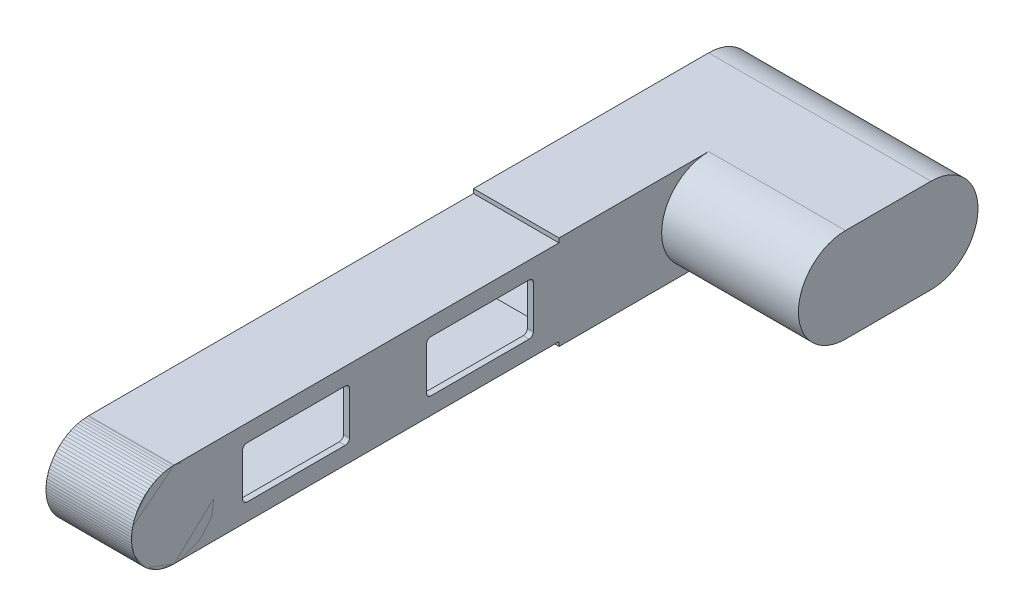
SolidWorks part; units mm, degrees
material "Cast Stainless Steel"
ref_plane "Front Plane" through (0, 0, 0) normal (0, 0, 1) x (1, 0, 0)
ref_plane "Top Plane" through (0, 0, 0) normal (0, 1, 0) x (1, 0, 0)
ref_plane "Right Plane" through (0, 0, 0) normal (1, 0, 0) x (0, 0, -1)
other "Center of Mass"
sketch "Sketch1" plane through (0, 0, 0) normal (1, 0, 0) x (0, 0, -1)
  line L0 (0, 0) -> (-500, 0) construction
  line L5 (-500, 50) -> (-50, 50)
  line L6 (50, -55) -> (-50, -55)
  line L7 (50, -55) -> (50, 55)
  line L8 (50, 55) -> (-50, 55)
  line L9 (-50, -55) -> (-50, 55)
  line L10 (50, -55) -> (-50, 55) construction
  line L11 (50, 55) -> (-50, -55) construction
  line L12 (-500, -50) -> (-50, -50)
  line L13 (0, 0) -> (280, 0)
  line L15 (280, 0) -> (50, 0)
  line L16 (280, 0) -> (280, 55)
  line L17 (280, 55) -> (50, 55)
  line L18 (50, 0) -> (50, 55)
  line L19 (280, 0) -> (50, 0)
  line L20 (280, 0) -> (280, -55)
  line L21 (280, -55) -> (50, -55)
  line L22 (50, 0) -> (50, -55)
  circle A0 centre (-500, 0) radius 50
  dimension "D1" = 100
  dimension "D2" = 110
  dimension "D3" = 100
  dimension "D4" = 500
  dimension "D5" = 280
extrude "Boss-Extrude1" add sketch "Sketch1" along normal blind 100 contours A0 L9 | A0 | L9 L6 L7 L8 | L21 L20 L13 L7 | L16 L17 L7 L13 region at (0, 0, 255.5167) region at (0, 0, 500) region at (0, 52.5, 48.5134) region at (0, 27.5, -165) region at (0, -27.5, -165)
sketch "Sketch2" plane through (0, 55, 0) normal (0, 1, 0) x (1, 0, 0)
  line L0 (0, 280) -> (260, 280)
  line L1 (260, 280) -> (260, 70)
  line L2 (260, 70) -> (100, 70)
  line L4 (0, 280) -> (0, -50)
  line L5 (0, -50) -> (100, -50)
  line L6 (100, -50) -> (100, 280)
  line L7 (100, 280) -> (0, 280)
  line L8 (0, 280) -> (0, -50)
  line L10 (100, -50) -> (100, 280)
  line L11 (100, 280) -> (0, 280)
  line L15 (0, -50) -> (100, -50)
  line M9 (100, -50) -> (100, 280)
  dimension "D2" = 260
  dimension "D3" = 210
  dimension "D1" = 0
extrude "Boss-Extrude2" add sketch "Sketch2" against normal up to surface (110 mm away) contours L2 L1 L0 M9 region at (180, 55, -175) up to face at (50, -55, -115)
sketch "Sketch3" plane through (260, 0, 0) normal (1, 0, 0) x (0, 0, -1)
  line L4 (70, -55) -> (280, -55)
  line L5 (280, -55) -> (280, 55)
  line L6 (280, 55) -> (70, 55)
  line L7 (70, 55) -> (70, -55)
  line L8 (70, -55) -> (280, -55)
  line L9 (280, -55) -> (280, 55)
  line L10 (280, 55) -> (70, 55)
  line L11 (70, 55) -> (70, -55)
  circle A0 centre (125, 0) radius 55
  circle A1 centre (225, 0) radius 55
  line M5 (70, -55) -> (280, -55)
  line M6 (280, -55) -> (280, 55)
  line M7 (280, 55) -> (70, 55)
  line M8 (70, 55) -> (70, -55)
  dimension "D1" = 0
extrude "Cut-Extrude1" cut sketch "Sketch3" against normal up to surface (260 mm away) contours A1 L9 M7 | A1 M5 M6 region at (260, -42.7148, -267.7148) region at (260, 42.7148, -267.7148) up to face at (0, 0, 86.25)
extrude "Cut-Extrude2" cut sketch "Sketch3<3>" against normal up to surface (160 mm away) contours A0 L10 M8 | A0 L11 M5 region at (260, -42.7148, -82.2852) region at (260, 42.7148, -82.2852) up to face at (100, 0, 138.75)
sketch "Sketch3<3>" plane through (260, 0, 0) normal (1, 0, 0) x (0, 0, -1) same geometry as "Sketch3"
extrude "Boss-Extrude3" add sketch "Sketch1<3>" along normal blind 100 separate body contours A0 region at (0, 0, 500)
sketch "Sketch1<3>" plane through (0, 0, 0) normal (1, 0, 0) x (0, 0, -1) same geometry as "Sketch1"
ref_plane "Plane1" through (-27.37, 0, 0) normal (-1, 0, 0) x (0, 0, 1)
sketch "Sketch11" plane through (-27.37, 0, 0) normal (-1, 0, 0) x (0, 0, 1)
  point P0 (0, 0)
  point P1 (0, 0)
  point P6 (0, 0)
sketch "Sketch12" plane through (0, 0, 0) normal (-1, 0, 0) x (0, 0, 1)
  line L0 (500, 0) -> (-225, 0) construction
  line L1 (85, 30) -> (200, 30)
  line L2 (80, 25) -> (80, -25)
  line L3 (85, -30) -> (200, -30)
  line L4 (205, 25) -> (205, -25)
  line L5 (250, 30) -> (250, -35.6293) construction
  line L6 (-225, -55) -> (50, -55)
  line L7 (50, -55) -> (50, -50)
  line L8 (50, -50) -> (500, -50)
  line L9 (500, 50) -> (50, 50)
  line L10 (50, 50) -> (50, 55)
  line L11 (50, 55) -> (-225, 55)
  line L12 (-225, -55) -> (50, -55)
  line L13 (50, -55) -> (50, -50)
  line L14 (50, -50) -> (500, -50)
  line L15 (500, 50) -> (50, 50)
  line L16 (50, 50) -> (50, 55)
  line L17 (50, 55) -> (-225, 55)
  line L22 (415, -30) -> (300, -30)
  line L23 (420, 25) -> (420, -25)
  line L24 (295, 25) -> (295, -25)
  line L25 (415, 30) -> (300, 30)
  arc A0 (415, 30) -> (420, 25) centre (415, 25) cw
  arc A1 (415, -30) -> (420, -25) centre (415, -25) ccw
  arc A2 (-225, 55) -> (-225, -55) centre (-225, 0) ccw
  arc A3 (500, -50) -> (500, 50) centre (500, 0) ccw
  arc A4 (-225, 55) -> (-225, -55) centre (-225, 0) ccw
  arc A5 (500, -50) -> (500, 50) centre (500, 0) ccw
  arc A6 (295, 25) -> (300, 30) centre (300, 25) cw
  arc A7 (295, -25) -> (300, -30) centre (300, -25) ccw
  arc A8 (205, 25) -> (200, 30) centre (200, 25) ccw
  arc A9 (205, -25) -> (200, -30) centre (200, -25) cw
  arc A10 (85, 30) -> (80, 25) centre (85, 25) ccw
  arc A11 (80, -25) -> (85, -30) centre (85, -25) ccw
  point P22 (420, 30)
  point P25 (420, -30)
  point P28 (295, 30)
  point P31 (295, -30)
  point P36 (205, 30)
  point P39 (205, -30)
  point P42 (80, 30)
  point P45 (80, -30)
  dimension "D6" = 5
  dimension "D2" = 125
  dimension "D3" = 60
  dimension "D4" = 80
  dimension "D5" = 45
  dimension "D1" = 0
extrude "Cut-Extrude3" cut sketch "Sketch12" against normal up to surface (100 mm away) contours L4 L1 L2 L3 | L23 L25 L24 L22 region at (0, 0, 142.5) region at (0, 0, 357.5) up to face at (100, 0, 131.875)
sketch "Sketch13" plane through (100, 0, 0) normal (1, 0, 0) x (0, 0, -1)
  line L0 (-50, -48) -> (125, -48)
  line L1 (125, -48) -> (225, -48)
  line L2 (125, -55) -> (225, -55)
  line L3 (225, 55) -> (125, 55)
  line L4 (125, -55) -> (225, -55)
  line L5 (225, 55) -> (125, 55)
  line L6 (-50, -55) -> (125, -55)
  line L7 (125, 55) -> (-50, 55)
  line L8 (-50, 55) -> (-50, 50)
  line L9 (-50, 50) -> (-500, 50)
  line L10 (-500, -50) -> (-50, -50)
  line L11 (-50, -50) -> (-50, -55)
  line L12 (-50, -55) -> (125, -55)
  line L13 (125, 55) -> (-50, 55)
  line L14 (-50, 55) -> (-50, 50)
  line L15 (-50, 50) -> (-500, 50)
  line L16 (-500, -50) -> (-50, -50)
  line L17 (-50, -50) -> (-50, -55)
  line L18 (225, 48) -> (125, 48)
  line L19 (125, 48) -> (-50, 48)
  line L20 (-43, 55) -> (-43, 50)
  line L21 (-50, 43) -> (-500, 43)
  line L22 (-50, -55) -> (225, -55)
  line L23 (-50, -50) -> (-50, -55)
  line L24 (-500, -50) -> (-50, -50)
  line L25 (-50, 50) -> (-500, 50)
  line L26 (-50, 55) -> (-50, 50)
  line L27 (225, 55) -> (-50, 55)
  line L28 (-50, -55) -> (225, -55)
  line L29 (-50, -50) -> (-50, -55)
  line L30 (-500, -50) -> (-50, -50)
  line L31 (-50, 50) -> (-500, 50)
  line L32 (-50, 55) -> (-50, 50)
  line L33 (225, 55) -> (-50, 55)
  line L34 (-500, -43) -> (-50, -43)
  line L35 (-43, -50) -> (-43, -55)
  line L36 (-50, -48) -> (225, -48)
  line L37 (225, 48) -> (-50, 48)
  line L38 (-43, -50) -> (-43, -55)
  line L39 (-500, -43) -> (-50, -43)
  line L40 (-50, 43) -> (-500, 43)
  line L41 (-43, 55) -> (-43, 50)
  line L42 (-50, -48) -> (-50, -43)
  line L43 (-50, 43) -> (-50, 48)
  arc A0 (225, -48) -> (225, 48) centre (225, 0) ccw
  arc A1 (225, -48) -> (225, 48) centre (225, 0) ccw
  arc A2 (125, 55) -> (125, -55) centre (125, 0) ccw
  arc A3 (-500, 50) -> (-500, -50) centre (-500, 0) ccw
  arc A5 (-500, 50) -> (-500, -50) centre (-500, 0) ccw
  arc A6 (125, 55) -> (125, -55) centre (125, 0) ccw
  arc A7 (225, -55) -> (225, 55) centre (225, 0) ccw
  arc A8 (-500, 43) -> (-500, -43) centre (-500, 0) ccw
  arc A9 (225, -55) -> (225, 55) centre (225, 0) ccw
  arc A10 (225, -55) -> (225, 55) centre (225, 0) ccw
  arc A11 (-500, 50) -> (-500, -50) centre (-500, 0) ccw
  arc A12 (225, -55) -> (225, 55) centre (225, 0) ccw
  arc A13 (-500, 50) -> (-500, -50) centre (-500, 0) ccw
  arc A14 (-500, 43) -> (-500, -43) centre (-500, 0) ccw
  line M21 (-415, 30) -> (-300, 30)
  line M22 (-295, 25) -> (-295, -25)
  line M23 (-300, -30) -> (-415, -30)
  line M24 (-420, -25) -> (-420, 25)
  arc M26 (125, -55) -> (125, 55) centre (125, 0) cw
  line M33 (-85, -30) -> (-200, -30)
  line M34 (-205, -25) -> (-205, 25)
  line M35 (-200, 30) -> (-85, 30)
  line M36 (-80, 25) -> (-80, -25)
  dimension "D1" = 0
  dimension "D2" = 0
  dimension "D3" = 0
  dimension "D4" = 7
extrude "Cut-Extrude4" cut sketch "Sketch13" against normal offset from surface (86 mm away) 7 from offset 7 contours L21 A8 L34 L42 L0 L19 L43 M26 M36 M33 M34 M35 M24 M21 M22 M23 | L1 A0 L18 L19 L0 M26 region at (100, 0, 222.0795) region at (100, 0, -170.5672) up to face at (0, 0, 142.5) offset against normal yes
